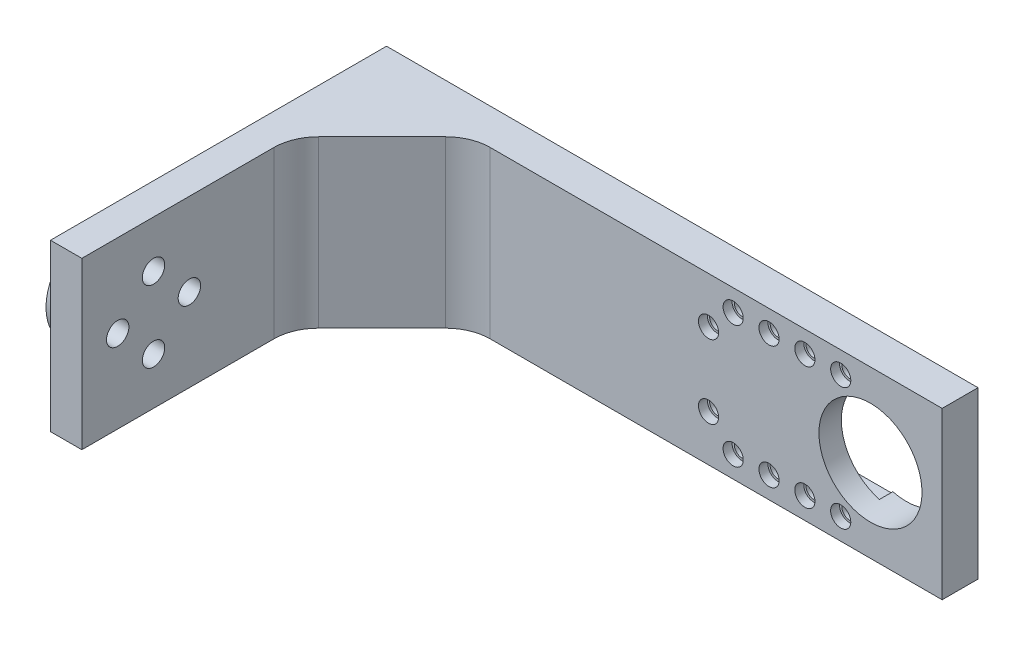
SolidWorks part; units mm, degrees
ref_plane "Front Plane" through (0, 0, 0) normal (0, 0, 1) x (1, 0, 0)
ref_plane "Top Plane" through (0, 0, 0) normal (0, 1, 0) x (1, 0, 0)
ref_plane "Right Plane" through (0, 0, 0) normal (1, 0, 0) x (0, 0, -1)
sketch "Sketch1" plane through (0, 0, 0) normal (0, 1, 0) x (1, 0, 0)
  line L0 (0, 0) -> (0, 75)
  line L1 (0, 75) -> (132, 75)
  line L2 (132, 75) -> (132, 67)
  line L3 (132, 67) -> (7, 67)
  line L4 (7, 67) -> (7, 0)
  line L5 (7, 0) -> (0, 0)
  dimension "D1" = 125
  dimension "D2" = 132
  dimension "D3" = 8
  dimension "D4" = 67
  dimension "D5" = 75
extrude "Boss-Extrude1" add sketch "Sketch1" along normal blind 37
sketch "Sketch2" plane through (0, 0, -75) normal (0, 0, -1) x (-1, 0, 0)
  line L0 (-132, 18.5) -> (-116, 18.5)
  line L1 (-132, 37) -> (-132, 0) construction
  circle A0 centre (-116, 18.5) radius 11.5
  dimension "D2" = 23
  dimension "D1" = 16
extrude "Cut-Extrude1" cut sketch "Sketch2" against normal up to next contours A0 region at (116, 7.3253, -75)
sketch "Sketch3" plane through (0, 0, -75) normal (0, 0, -1) x (-1, 0, 0)
  line L0 (-132, 32.19) -> (-109.36, 32.19)
  line L1 (-132, 37) -> (-132, 0) construction
  line L2 (-109.36, 32.19) -> (-109.36, 37)
  line L3 (-132, 37) -> (0, 37) construction
  line L4 (-132, 18.5) -> (-57.038, 18.5)
  circle A0 centre (-109.36, 32.19) radius 1.75
  circle A1 centre (-101.36, 32.19) radius 1.75
  circle A2 centre (-93.36, 32.19) radius 1.75
  circle A3 centre (-85.36, 32.19) radius 1.75
  circle A4 centre (-85.36, 4.81) radius 1.75
  circle A5 centre (-93.36, 4.81) radius 1.75
  circle A6 centre (-101.36, 4.81) radius 1.75
  circle A7 centre (-109.36, 4.81) radius 1.75
  circle A8 centre (-79.86, 26.69) radius 1.75
  circle A9 centre (-79.86, 10.31) radius 1.75
  dimension "D3" = 3.5
  dimension "D9" = 3.5
  dimension "D10" = 3.5
  dimension "D1" = 22.64
  dimension "D2" = 4.81
  dimension "D4" = 4
extrude "Cut-Extrude2" cut sketch "Sketch3" against normal up to next contours A5 | A8 | A9 | A7 | A6 | A4 | A3 | A2 | A1 | A0 region at (93.36, 4.81, -75) region at (79.86, 26.69, -75) region at (79.86, 10.31, -75)
sketch "Sketch4" plane through (0, 0, -75) normal (0, 0, -1) x (-1, 0, 0)
  line L0 (-113, 30) -> (-113, 7)
  line L4 (-113, 30) -> (-75, 30)
  line L5 (-75, 30) -> (-75, 7)
  line L6 (-75, 7) -> (-113, 7)
  dimension "D3" = 23
  dimension "D4" = 38
  dimension "D5" = 38
sketch "Sketch5" plane through (0, 0, 0) normal (-1, 0, 0) x (0, 0, 1)
  circle A1 centre (-16, 10.5) radius 1.75
  circle A2 centre (-24, 18.5) radius 1.75
  circle A3 centre (-16, 26.5) radius 1.75
  circle A4 centre (-8, 18.5) radius 1.75
  point P13 (-16, 18.5)
  dimension "D4" = 3.5
  dimension "D1" = 4
extrude "Cut-Extrude5" cut sketch "Sketch5" against normal up to next
sketch "Sketch6" plane through (0, 0, 0) normal (-1, 0, 0) x (0, 0, 1)
  line L0 (0, 18.5) -> (-16, 18.5)
  line L1 (0, 37) -> (0, 0) construction
  circle A0 centre (-16, 18.5) radius 11
  circle A1 centre (-16, 10.5) radius 1.75 construction
  circle A2 centre (-24, 18.5) radius 1.75 construction
  circle A3 centre (-16, 26.5) radius 1.75 construction
  circle A4 centre (-8, 18.5) radius 1.75 construction
  circle A5 centre (-16, 10.5) radius 1.75
  circle A6 centre (-24, 18.5) radius 1.75
  circle A7 centre (-16, 26.5) radius 1.75
  circle A8 centre (-8, 18.5) radius 1.75
  circle M1 centre (-8, 18.5) radius 1.75
  circle M2 centre (-16, 26.5) radius 1.75
  circle M3 centre (-24, 18.5) radius 1.75
  circle M4 centre (-16, 10.5) radius 1.75
  dimension "D2" = 22
  dimension "D1" = 16
extrude "Boss-Extrude3" add sketch "Sketch6" along normal blind 6 contours A0 M1 M3 M4 M2 region at (0, 18.5, -26.6889)
extrude "Cut-Extrude6" cut sketch "Sketch4" against normal blind 3
sketch "Sketch7" plane through (75, 0, 0) normal (1, 0, 0) x (0, 0, -1)
  line L4 (75, 7) -> (75, 30)
  line L5 (75, 30) -> (72, 30)
  line L6 (72, 30) -> (72, 7)
  line L7 (72, 7) -> (75, 7)
  line L8 (75, 7) -> (75, 30)
  line L9 (75, 30) -> (72, 30)
  line L10 (72, 30) -> (72, 7)
  line L11 (72, 7) -> (75, 7)
  dimension "D1" = 0
extrude "Boss-Extrude4" add sketch "Sketch7" along normal blind 7.5
sketch "Sketch8" plane through (0, 0, -67) normal (0, 0, 1) x (1, 0, 0)
  circle A1 centre (79.86, 10.31) radius 1.75
  circle A2 centre (79.86, 10.31) radius 1.75
  circle A3 centre (79.86, 26.69) radius 1.75
  circle A4 centre (79.86, 26.69) radius 1.75
  dimension "D1" = 0
  dimension "D2" = 0
extrude "Cut-Extrude7" cut sketch "Sketch8" against normal up to next
sketch "Sketch9" plane through (0, 0, -67) normal (0, 0, 1) x (1, 0, 0)
  circle A0 centre (79.86, 26.69) radius 2.25
  circle A1 centre (85.36, 32.19) radius 2.25
  circle A2 centre (93.36, 32.19) radius 2.25
  circle A3 centre (101.36, 32.19) radius 2.25
  circle A4 centre (109.36, 32.19) radius 2.25
  circle A5 centre (79.86, 10.31) radius 2.25
  circle A6 centre (85.36, 4.81) radius 2.25
  circle A7 centre (93.36, 4.81) radius 2.25
  circle A8 centre (101.36, 4.81) radius 2.25
  circle A9 centre (109.36, 4.81) radius 2.25
  dimension "D1" = 4.5
  dimension "D2" = 4.5
  dimension "D3" = 4.5
  dimension "D4" = 4.5
  dimension "D5" = 4.5
  dimension "D6" = 4.5
  dimension "D7" = 4.5
  dimension "D8" = 4.5
  dimension "D9" = 4.5
  dimension "D10" = 4.5
extrude "Cut-Extrude8" cut sketch "Sketch9" against normal blind 2
sketch "Sketch10" plane through (7, 0, 0) normal (1, 0, 0) x (0, 0, -1)
  circle A0 centre (24, 18.5) radius 2.5
  circle A1 centre (16, 10.5) radius 2.5
  circle A2 centre (8, 18.5) radius 2.5
  circle A3 centre (16, 26.5) radius 2.5
  dimension "D1" = 5
  dimension "D2" = 5
  dimension "D3" = 5
  dimension "D4" = 5
extrude "Cut-Extrude9" cut sketch "Sketch10" against normal blind 5
chamfer "Chamfer1" distance 20 angle 45 1 edges at (7, 18.5, -67)
fillet "Fillet5" radius 10 2 edges at (7, 18.5, -47) (27, 18.5, -67)
